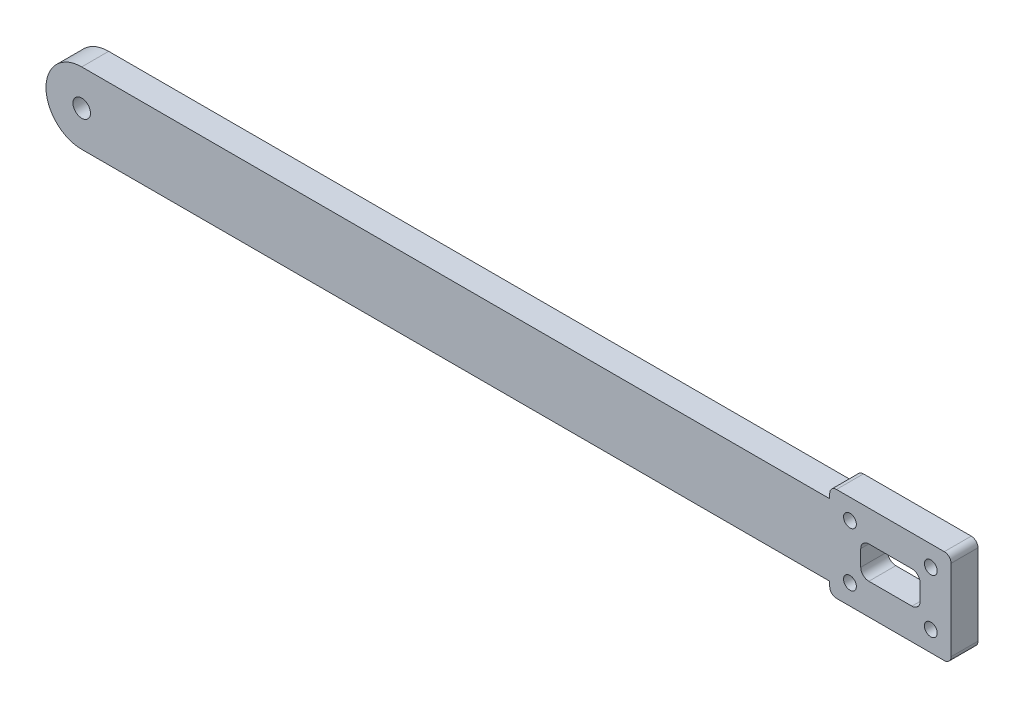
SolidWorks part; units mm, degrees
ref_plane "Front Plane" through (0, 0, 0) normal (0, 0, 1) x (1, 0, 0)
ref_plane "Top Plane" through (0, 0, 0) normal (0, 1, 0) x (1, 0, 0)
ref_plane "Right Plane" through (0, 0, 0) normal (1, 0, 0) x (0, 0, -1)
sketch "Sketch1" plane through (0, 0, 0) normal (0, 0, 1) x (1, 0, 0)
  line L0 (0, 0) -> (300, 0) construction
  line L1 (0, 13.25) -> (300, 13.25)
  line L2 (0, -13.25) -> (300, -13.25)
  line L3 (285, 10) -> (315, 10) construction
  line L4 (277.5, -17.5) -> (322.5, -17.5)
  line L5 (277.5, -17.5) -> (277.5, 17.5)
  line L6 (277.5, 17.5) -> (322.5, 17.5)
  line L7 (322.5, -17.5) -> (322.5, 17.5)
  line L8 (300, 17.5) -> (300, -17.5) construction
  line L9 (277.5, 0) -> (322.5, 0) construction
  line L10 (285, 10) -> (285, -10) construction
  line L12 (292, -6) -> (308, -6)
  line L13 (289, -3) -> (289, 3)
  line L14 (292, 6) -> (308, 6)
  line L15 (311, -3) -> (311, 3)
  line L16 (289, -6) -> (311, 6) construction
  line L17 (289, 6) -> (311, -6) construction
  arc A0 (0, 13.25) -> (0, -13.25) centre (0, 0) ccw
  arc A1 (300, -13.25) -> (300, 13.25) centre (300, 0) ccw
  circle A2 centre (0, 0) radius 3.25
  circle A3 centre (285, 10) radius 2.375
  circle A4 centre (315, 10) radius 2.375
  circle A5 centre (285, -10) radius 2.375
  circle A6 centre (315, -10) radius 2.375
  arc A7 (289, 3) -> (292, 6) centre (292, 3) cw
  arc A8 (311, 3) -> (308, 6) centre (308, 3) ccw
  arc A9 (308, -6) -> (311, -3) centre (308, -3) ccw
  arc A10 (292, -6) -> (289, -3) centre (292, -3) cw
  arc A11 (0, 13.25) -> (0, -13.25) centre (0, 0) cw
  point P3 (150, 0)
  point P10 (300, 0)
  point P21 (300, 10)
  point P25 (285, 0)
  point P26 (300, 0)
  point P30 (300, 0)
  point P51 (0, 0)
  dimension "D1" = 6.5
  dimension "D4" = 4.75
  dimension "D11" = 3
  dimension "D2" = 10
  dimension "D3" = 300
  dimension "D5" = 30
  dimension "D6" = 20
  dimension "D7" = 7.5
  dimension "D8" = 7.5
  dimension "D9" = 4
  dimension "D10" = 4
extrude "Main Arm" add sketch "Sketch1" along normal blind 10 contours L1 A0 L2 L5 A2 | L2 A1 L1 L5 A3 A5 | A1 L2 L5 L4 L7 L6 L1 A6 A4 | A11 A0 A2 region at (12.8752, 0, 0) region at (143.9369, 0, 0) region at (278.0701, 15.375, 0) region at (288.75, 12.805, 0)
fillet "Fillet1" radius 2.5 4 edges at (277.5, -17.5, 5) (322.5, -17.5, 5) (322.5, 17.5, 5) (277.5, 17.5, 5)
equation "\"D8@Sketch1\"=\"D7@Sketch1\""
